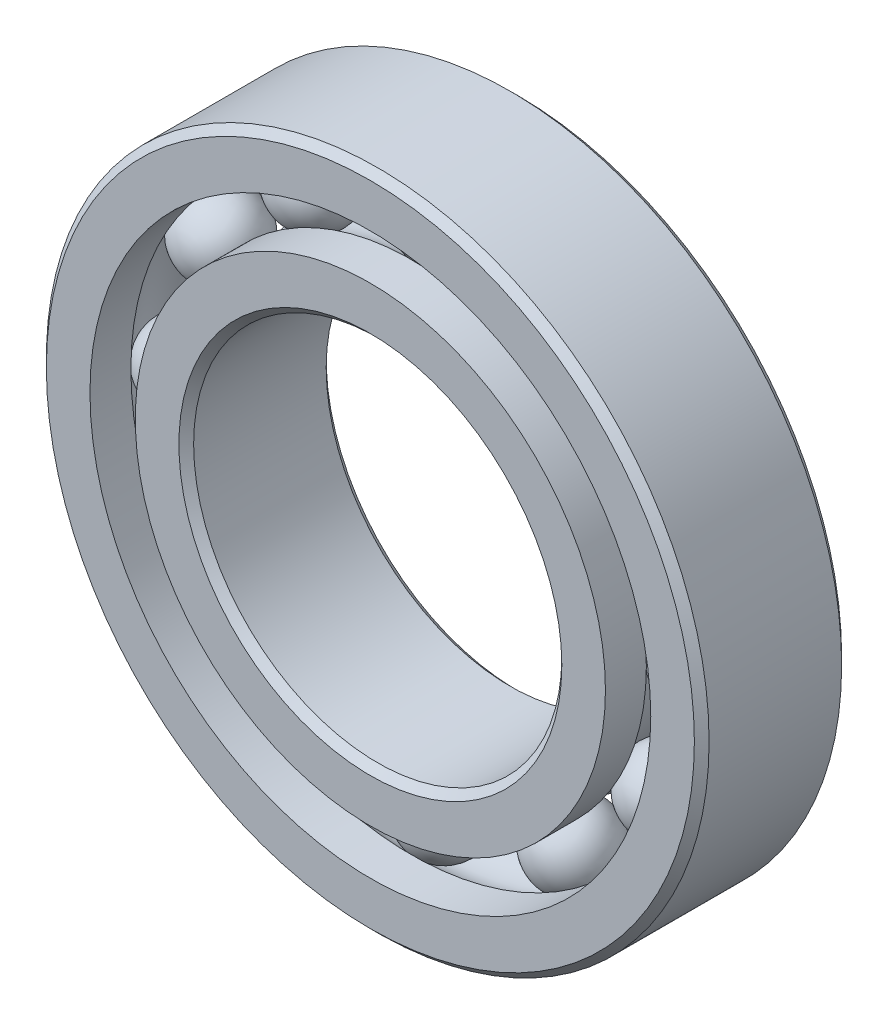
SolidWorks part; units mm, degrees
ref_plane "Front Plane" through (0, 0, 0) normal (0, 0, 1) x (1, 0, 0)
ref_plane "Top Plane" through (0, 0, 0) normal (0, 1, 0) x (1, 0, 0)
ref_plane "Right Plane" through (0, 0, 0) normal (1, 0, 0) x (0, 0, -1)
sketch "Sketch1" plane through (0, 0, 0) normal (1, 0, 0) x (0, 0, -1)
  line L0 (-10, 0) -> (10, 0) construction
  line L1 (0, 45) -> (0, -45) construction
  line L2 (9, 45) -> (-9, 45)
  line L3 (-9, 45) -> (-10, 44)
  line L4 (-10, 44) -> (-10, 38.0769)
  line L5 (-10, 38.0769) -> (-4.4444, 38.0769)
  line L6 (10, 38.0769) -> (4.4444, 38.0769)
  line L7 (10, 44) -> (10, 38.0769)
  line L8 (9, 45) -> (10, 44)
  line L9 (0, 45) -> (0, 35) construction
  line L10 (0, 35) -> (0, 25) construction
  arc A0 (-4.4444, 38.0769) -> (4.4444, 38.0769) centre (0, 35) cw
  point P14 (0, 25)
  dimension "Width" = 20
  dimension "OD" = 90
  dimension "D1" = 45
  dimension "D2" = 1
  dimension "Shaft Dia" = 50
  dimension "D3" = 8.8889
  dimension "D4" = 3.0769
revolve "Revolve1" add sketch "Sketch1" angle 360 about L0
sketch "Sketch3" plane through (0, 0, 0) normal (1, 0, 0) x (0, 0, -1)
  line L0 (-10, 31.9231) -> (-4.4444, 31.9231)
  line L1 (0, 45) -> (0, -45) construction
  line L2 (-10, 44) -> (-10, 38.0769) construction
  line L3 (-10, 31.9231) -> (-10, 26)
  line L4 (-9, 45) -> (-10, 44) construction
  line L5 (-10, 26) -> (-9, 25)
  line L6 (-9, 25) -> (9, 25)
  line L7 (9, 45) -> (9, -45) construction
  line L8 (9, 25) -> (10, 26)
  line L9 (10, -44) -> (10, 44) construction
  line L10 (10, 26) -> (10, 31.9231)
  line L11 (10, 31.9231) -> (4.4444, 31.9231)
  line L13 (9, 45) -> (10, 44) construction
  arc A0 (4.4444, 38.0769) -> (-4.4444, 38.0769) centre (0, 35) ccw construction
  arc A1 (4.4444, 31.9231) -> (-4.4444, 31.9231) centre (0, 35) cw
revolve "Revolve3" add sketch "Sketch3" angle 360 about L0
sketch "Sketch4" plane through (0, 0, 0) normal (1, 0, 0) x (0, 0, -1)
  line L0 (-5.4056, 35) -> (5.4056, 35)
  arc A2 (-5.4056, 35) -> (5.4056, 35) centre (0, 35) cw
  arc A3 (4.4444, 38.0769) -> (-4.4444, 38.0769) centre (0, 35) ccw construction
revolve "Revolve4" add sketch "Sketch4" angle 360 about L0
ref_axis "Axis1" through (0, 0, -10) along (0, 0, 1)
pattern_circular "CirPattern1" count 12 every 30 about axis through (0, 0, -10) along (0, 0, 1) of bodies 104
sketch "Sketch5" plane through (0, 0, 0) normal (1, 0, 0) x (0, 0, -1)
  line L0 (-10, 38.0769) -> (-4.4444, 38.0769) construction
  line L1 (-9.5, 38.0769) -> (-5.4056, 38.0769)
  line L2 (-9.5, 38.0769) -> (-9.5, 31.9231)
  line L3 (-9.5, 31.9231) -> (-5.4056, 31.9231)
  line L4 (-5.4056, 38.0769) -> (-5.4056, 31.9231)
  line L5 (-10, 31.9231) -> (-4.4444, 31.9231) construction
  line L6 (10, 38.0769) -> (4.4444, 38.0769) construction
  line L7 (9.5, 38.0769) -> (5.4056, 38.0769)
  line L8 (9.5, 38.0769) -> (9.5, 31.9231)
  line L9 (9.5, 31.9231) -> (5.4056, 31.9231)
  line L10 (5.4056, 38.0769) -> (5.4056, 31.9231)
  line L11 (10, 31.9231) -> (4.4444, 31.9231) construction
  line L12 (-9, 45) -> (-10, 44) construction
  point P18 (-9.5, 44.5)
revolve "Revolve5" [suppressed] add sketch "Sketch5" angle 360 about L0
equation "\"D2@Sketch1\" = \"Width@Sketch1\"*.05"
equation "\"D3@Sketch1\" = \"Width@Sketch1\"/2.25"
equation "\"D4@Sketch1\" = (((\"OD@Sketch1\"-\"Width@Sketch1\")/2)/3.25)/3.5"
equation "\"D2@CirPattern1\" = 360/\"Balls@CirPattern1\""
